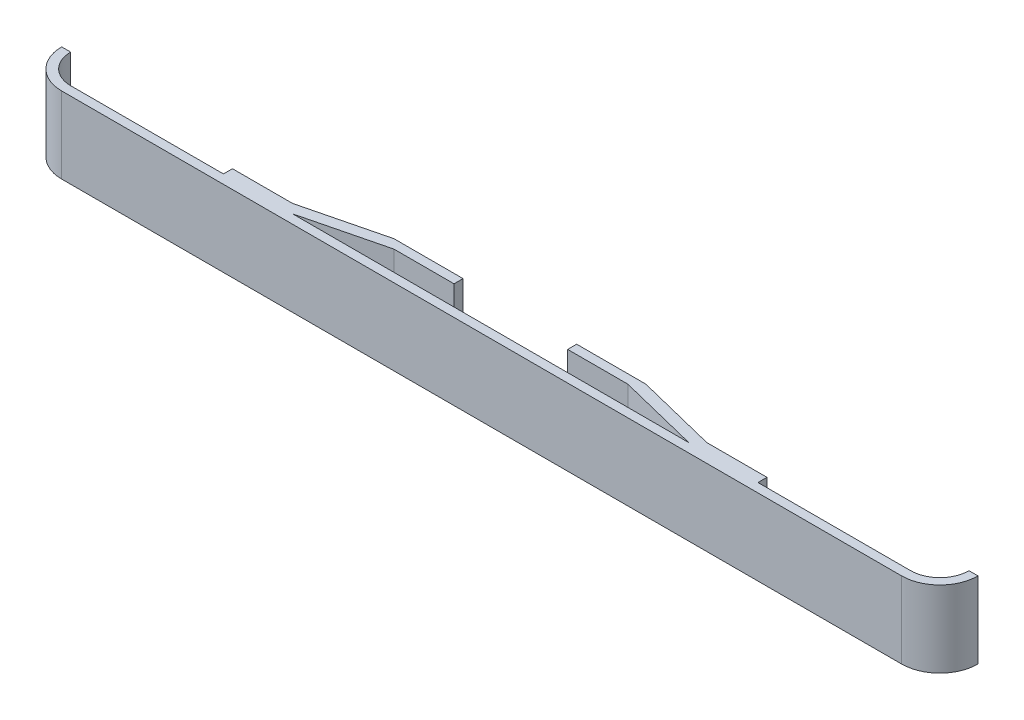
SolidWorks part; units mm, degrees
material "ABS"
ref_plane "Front Plane" through (0, 0, 0) normal (0, 0, 1) x (1, 0, 0)
ref_plane "Top Plane" through (0, 0, 0) normal (0, 1, 0) x (1, 0, 0)
ref_plane "Right Plane" through (0, 0, 0) normal (1, 0, 0) x (0, 0, -1)
sketch "Sketch1" plane through (0, 0, 0) normal (0, 0, 1) x (1, 0, 0)
  line L1 (-26.033, 10.5636) -> (278.767, 10.5636)
  line L2 (-26.033, 10.5636) -> (-26.033, -14.8364)
  line L3 (-26.033, -14.8364) -> (278.767, -14.8364)
  line L4 (278.767, 10.5636) -> (278.767, -14.8364)
  dimension "D1" = 25.4
  dimension "D2" = 304.8
extrude "Boss-Extrude2" add sketch "Sketch1" along normal blind 12.7 contours L1 L4 L3 L2
fillet "Fillet1" radius 12.7 2 edges at (-26.033, -2.1364, 12.7) (278.767, -2.1364, 12.7)
sketch "Sketch6" plane through (0, 10.5636, 0) normal (0, 1, 0) x (1, 0, 0)
  line L5 (-23.033, 0) -> (275.767, 0)
  line L6 (-13.333, -9.7) -> (266.067, -9.7)
  line L7 (-13.333, -9.7) -> (266.067, -9.7)
  arc A8 (266.067, -9.7) -> (275.767, 0) centre (266.067, 0) ccw
  arc A9 (-23.033, 0) -> (-13.333, -9.7) centre (-13.333, 0) ccw
  arc A10 (266.067, -9.7) -> (275.767, 0) centre (266.067, 0) ccw
  arc A11 (-23.033, 0) -> (-13.333, -9.7) centre (-13.333, 0) ccw
  dimension "D1" = 3
extrude "Cut-Extrude3" cut sketch "Sketch6" against normal through all
sketch "Sketch8" plane through (0, 0, 9.7) normal (0, 0, -1) x (-1, 0, 0)
  line L0 (13.333, 10.5636) -> (-266.067, 10.5636) construction
  line L1 (-145.267, 10.5636) -> (-215.267, 10.5636)
  line L2 (-145.267, 10.5636) -> (-145.267, -14.8364)
  line L3 (-145.267, -14.8364) -> (-215.267, -14.8364)
  line L4 (-215.267, 10.5636) -> (-215.267, -14.8364)
  line L5 (13.333, -14.8364) -> (-266.067, -14.8364) construction
  line L6 (-266.067, -14.8364) -> (-266.067, 10.5636) construction
  line L7 (-37.467, 10.5636) -> (-107.467, 10.5636)
  line L8 (-37.467, 10.5636) -> (-37.467, -14.8364)
  line L9 (-37.467, -14.8364) -> (-107.467, -14.8364)
  line L10 (-107.467, 10.5636) -> (-107.467, -14.8364)
  line L11 (13.333, -14.8364) -> (13.333, 10.5636) construction
  dimension "D1" = 50.8
  dimension "D2" = 70
  dimension "D3" = 50.8
  dimension "D4" = 70
extrude "Boss-Extrude3" add sketch "Sketch8" along normal blind 9.7
sketch "Sketch9" plane through (0, 10.5636, 0) normal (0, 1, 0) x (1, 0, 0)
  line L0 (145.267, -9.7) -> (165.267, -9.7)
  line L1 (165.267, -9.7) -> (192.267, -9.7)
  line L2 (192.267, -9.7) -> (165.267, -3)
  line L3 (165.267, -3) -> (145.267, -3)
  line L4 (145.267, 0) -> (145.267, -9.7) construction
  line L5 (145.267, -3) -> (145.267, -9.7)
  line L6 (145.267, 0) -> (215.267, 0) construction
  line L7 (215.267, -6.7) -> (195.267, -6.7)
  line L8 (215.267, 0) -> (215.267, -9.7) construction
  line L9 (195.267, -6.7) -> (168.267, 0)
  line L10 (168.267, 0) -> (215.267, 0)
  line L11 (215.267, 0) -> (215.267, -6.7)
  dimension "D1" = 3
  dimension "D2" = 20
  dimension "D3" = 27
  dimension "D4" = 20
  dimension "D5" = 20
  dimension "D6" = 3
  dimension "D7" = 47
extrude "Cut-Extrude4" cut sketch "Sketch9" against normal through all
sketch "Sketch12" plane through (0, 10.5636, 0) normal (0, 1, 0) x (1, 0, 0)
  line L0 (107.467, -9.7) -> (107.467, -3)
  line L1 (107.467, 0) -> (107.467, -9.7) construction
  line L2 (107.467, -3) -> (87.467, -3)
  line L3 (87.467, -3) -> (60.467, -9.7)
  line L4 (60.467, -9.7) -> (107.467, -9.7)
  line L11 (37.467, -6.7) -> (57.467, -6.7)
  line L12 (37.467, 0) -> (37.467, -9.7) construction
  line L13 (57.467, -6.7) -> (84.467, 0)
  line L14 (37.467, 0) -> (107.467, 0) construction
  line L15 (84.467, 0) -> (37.467, 0)
  line L16 (37.467, 0) -> (37.467, -6.7)
  dimension "D1" = 3
  dimension "D2" = 20
  dimension "D3" = 47
  dimension "D4" = 3
  dimension "D5" = 20
  dimension "D6" = 47
extrude "Cut-Extrude5" cut sketch "Sketch12" against normal through all
